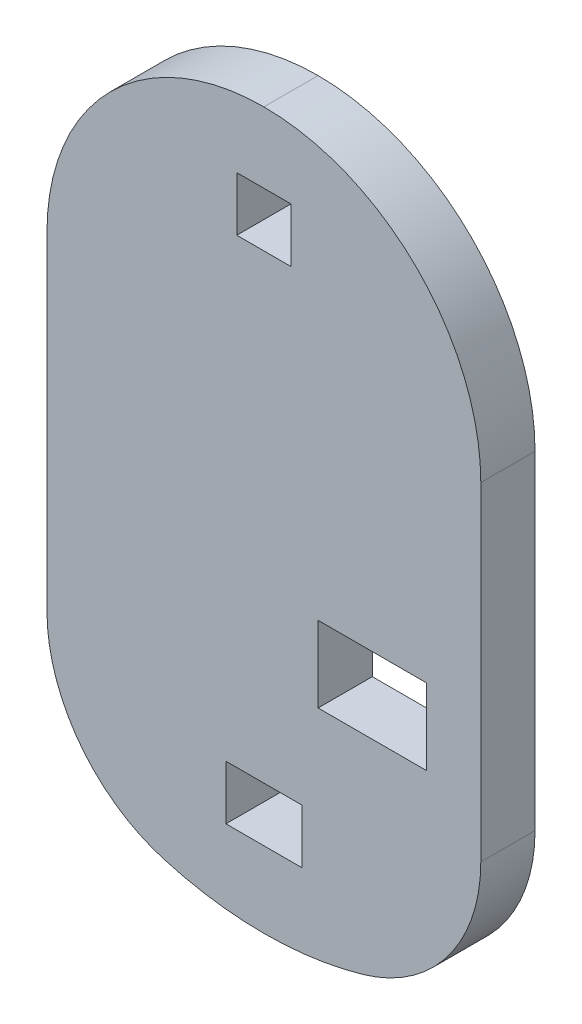
SolidWorks part; units mm, degrees
material "Acrylic (Medium-high impact)"
ref_plane "Front Plane" through (0, 0, 0) normal (0, 0, 1) x (1, 0, 0)
ref_plane "Top Plane" through (0, 0, 0) normal (0, 1, 0) x (1, 0, 0)
ref_plane "Right Plane" through (0, 0, 0) normal (1, 0, 0) x (0, 0, -1)
sketch "Sketch1" plane through (0, 0, 0) normal (0, 0, 1) x (1, 0, 0)
  circle A0 centre (0, 0) radius 33
  dimension "D1" = 66
extrude "Boss-Extrude1" add sketch "Sketch1" along normal blind 5
sketch "Sketch6" plane through (0, 0, 5) normal (0, 0, 1) x (1, 0, 0)
  line L0 (-20, 26.2488) -> (-20, -26.2488)
  line L1 (20, -26.2488) -> (20, 26.2488)
  arc A0 (20, -26.2488) -> (20, 26.2488) centre (0, 0) ccw
  circle A1 centre (0, 0) radius 33
  arc A2 (-20, 26.2488) -> (-20, -26.2488) centre (0, 0) ccw
  dimension "D2" = 20
  dimension "D3" = 40
  dimension "D1" = 0
extrude "Cut-Extrude3" cut sketch "Sketch6" against normal blind 10
fillet "Fillet2" radius 20 2 edges at (-20, 26.2488, 2.5) (20, 26.2488, 2.5)
fillet "Fillet3" radius 15 2 edges at (20, -26.2488, 2.5) (-20, -26.2488, 2.5)
sketch "Sketch7" plane through (0, 0, 5) normal (0, 0, 1) x (1, 0, 0)
  line L1 (-2.5, 26.5) -> (2.5, 26.5)
  line L2 (-2.5, 26.5) -> (-2.5, 21.5)
  line L3 (-2.5, 21.5) -> (2.5, 21.5)
  line L4 (2.5, 26.5) -> (2.5, 21.5)
  line L5 (-3.5, -21) -> (3.5, -21)
  line L6 (-3.5, -21) -> (-3.5, -26)
  line L7 (-3.5, -26) -> (3.5, -26)
  line L8 (3.5, -21) -> (3.5, -26)
  point P9 (0, 21.5)
  point P11 (0, -21)
  dimension "D1" = 6.5
  dimension "D2" = 42.5
  dimension "D3" = 5
  dimension "D4" = 5
  dimension "D5" = 7
extrude "Cut-Extrude4" cut sketch "Sketch7" against normal blind 10
sketch "Sketch2" plane through (0, 0, 5) normal (0, 0, 1) x (1, 0, 0)
  line L1 (-5, 26.5) -> (5, 26.5)
  line L2 (-5, 26.5) -> (-5, 21.5)
  line L3 (-5, 21.5) -> (5, 21.5)
  line L4 (5, 26.5) -> (5, 21.5)
  line L5 (-5, 26.5) -> (5, 21.5) construction
  line L6 (-5, 21.5) -> (5, 26.5) construction
  point P0 (0, 24)
  dimension "D1" = 5
  dimension "D2" = 26.5
  dimension "D3" = 10
extrude "Boss-Extrude2" [suppressed] add sketch "Sketch2" along normal blind 38
sketch "Sketch3" [suppressed] plane through (0, 26.5, 0) normal (0, 1, 0) x (1, 0, 0)
  line L0 (5, -5) -> (-5, -5) construction
  line L1 (5, -43) -> (-5, -43) construction
  circle A0 centre (0, -12) radius 0.5
  circle A1 centre (0, -14) radius 0.5
  circle A2 centre (0, -16) radius 0.5
  circle A3 centre (0, -18) radius 0.5
  circle A4 centre (0, -20) radius 0.5
  circle A5 centre (0, -22) radius 0.5
  circle A6 centre (0, -40.5) radius 0.5
  circle A7 centre (0, -38.5) radius 0.5
  circle A8 centre (0, -36.5) radius 0.5
  circle A9 centre (0, -34.5) radius 0.5
  circle A10 centre (0, -32.5) radius 0.5
  circle A11 centre (0, -30.5) radius 0.5
  point P20 (0, -43)
  dimension "D2" = 1
  dimension "D5" = 8.5
  dimension "D6" = 2
  dimension "D1" = 7
  dimension "D7" = 2
  dimension "D3" = 6
  dimension "D4" = 6
extrude "Cut-Extrude1" [suppressed] cut sketch "Sketch3" against normal blind 5
sketch "Sketch4" [suppressed] plane through (0, 0, 5) normal (0, 0, 1) x (1, 0, 0)
  line L1 (-7.5, -20.5) -> (7.5, -20.5)
  line L2 (-7.5, -20.5) -> (-7.5, -25.5)
  line L3 (-7.5, -25.5) -> (7.5, -25.5)
  line L4 (7.5, -20.5) -> (7.5, -25.5)
  line L5 (-7.5, -20.5) -> (7.5, -25.5) construction
  line L6 (-7.5, -25.5) -> (7.5, -20.5) construction
  line L7 (-5, 21.5) -> (5, 21.5) construction
  point P0 (0, -23)
  dimension "D1" = 42
  dimension "D2" = 15
  dimension "D3" = 5
extrude "Boss-Extrude3" [suppressed] add sketch "Sketch4" along normal blind 32
sketch "Sketch5" [suppressed] plane through (0, -20.5, 0) normal (0, 1, 0) x (1, 0, 0)
  line L0 (-7.5, -5) -> (-3.5, -5) construction
  circle A0 centre (0, -26.25) radius 3.8
  dimension "D1" = 21.25
  dimension "D2" = 7.6
extrude "Cut-Extrude2" [suppressed] cut sketch "Sketch5" against normal blind 28
fillet "Fillet4" [suppressed] radius 0.5
sketch "Sketch8" plane through (0, 0, 5) normal (0, 0, 1) x (1, 0, 0)
  line L0 (20, 13) -> (20, -17.2916) construction
  line L1 (5, -5.5) -> (15, -5.5)
  line L2 (5, -5.5) -> (5, -12.5)
  line L3 (5, -12.5) -> (15, -12.5)
  line L4 (15, -5.5) -> (15, -12.5)
  line L5 (3.5, -21) -> (-3.5, -21) construction
  dimension "D1" = 10
  dimension "D2" = 7
  dimension "D3" = 5
  dimension "D4" = 8.5
extrude "Cut-Extrude5" cut sketch "Sketch8" against normal blind 10
